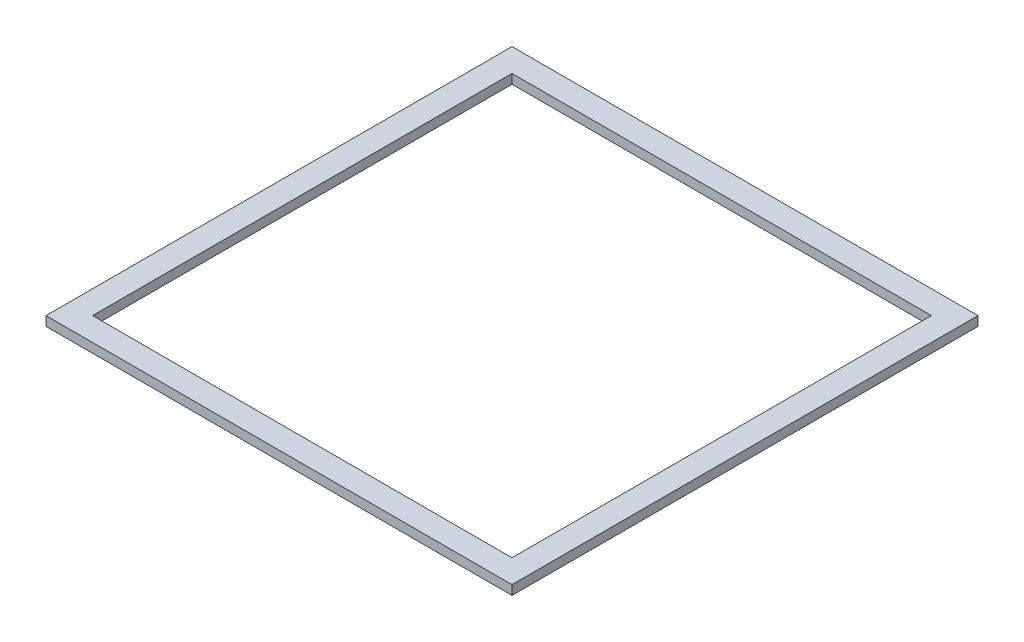
SolidWorks part; units mm, degrees
ref_plane "Front Plane" through (0, 0, 0) normal (0, 0, 1) x (1, 0, 0)
ref_plane "Top Plane" through (0, 0, 0) normal (0, 1, 0) x (1, 0, 0)
ref_plane "Right Plane" through (0, 0, 0) normal (1, 0, 0) x (0, 0, -1)
sketch "Sketch1" plane through (0, 0, 0) normal (0, 1, 0) x (1, 0, 0)
  line L1 (500, -500) -> (-500, -500)
  line L2 (500, -500) -> (500, 500)
  line L3 (500, 500) -> (-500, 500)
  line L4 (-500, -500) -> (-500, 500)
  line L5 (500, -500) -> (-500, 500) construction
  line L6 (500, 500) -> (-500, -500) construction
  line L7 (450, -450) -> (-450, -450)
  line L8 (450, -450) -> (450, 450)
  line L9 (450, 450) -> (-450, 450)
  line L10 (-450, -450) -> (-450, 450)
  line L11 (450, -450) -> (-450, 450) construction
  line L12 (450, 450) -> (-450, -450) construction
  point P0 (0, 0)
  point P6 (0, 0)
  dimension "D1" = 1000
  dimension "D2" = 1000
  dimension "D3" = 900
  dimension "D4" = 900
extrude "Boss-Extrude1" add sketch "Sketch1" along normal blind 20
